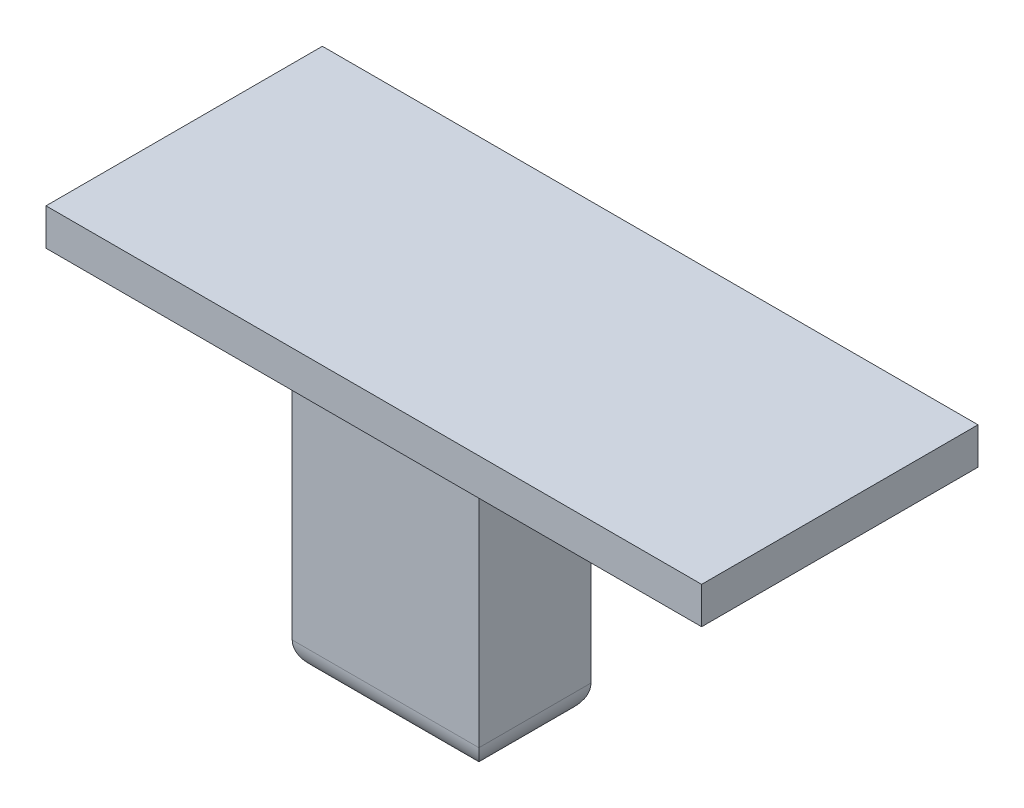
SolidWorks part; units mm, degrees
ref_plane "Front Plane" through (0, 0, 0) normal (0, 0, 1) x (1, 0, 0)
ref_plane "Top Plane" through (0, 0, 0) normal (0, 1, 0) x (1, 0, 0)
ref_plane "Right Plane" through (0, 0, 0) normal (1, 0, 0) x (0, 0, -1)
sketch "Sketch1" plane through (0, 0, 0) normal (0, 1, 0) x (1, 0, 0)
  line L0 (17.3, -2.8) -> (22.3, -2.8) construction
  line L1 (-22.3, 16) -> (22.3, 16)
  line L2 (-22.3, 16) -> (-22.3, -2.8)
  line L3 (-22.3, -2.8) -> (22.3, -2.8)
  line L4 (22.3, 16) -> (22.3, -2.8)
  dimension "D1" = 44.6
extrude "Boss-Extrude1" add sketch "Sketch1" against normal blind 2.5
sketch "Sketch2" plane through (0, 0, 0) normal (0, 1, 0) x (1, 0, 0)
  line L1 (6.35, -2) -> (-6.35, -2)
  line L2 (6.35, -2) -> (6.35, 5.62)
  line L3 (6.35, 5.62) -> (-6.35, 5.62)
  line L4 (-6.35, -2) -> (-6.35, 5.62)
  dimension "D1" = 12.7
  dimension "D2" = 7.62
  dimension "D3" = 2
  dimension "D4" = 6.35
extrude "Boss-Extrude2" add sketch "Sketch2" against normal blind 20
fillet "Fillet1" radius 2 4 edges at (0, -20, -5.62) (-6.35, -20, -1.81) (0, -20, 2) (6.35, -20, -1.81)
fillet "Fillet2" radius 0.5 4 edges at (-6.35, -2.5, -1.81) (0, -2.5, 2) (0, -2.5, -5.62) (6.35, -2.5, -1.81)
